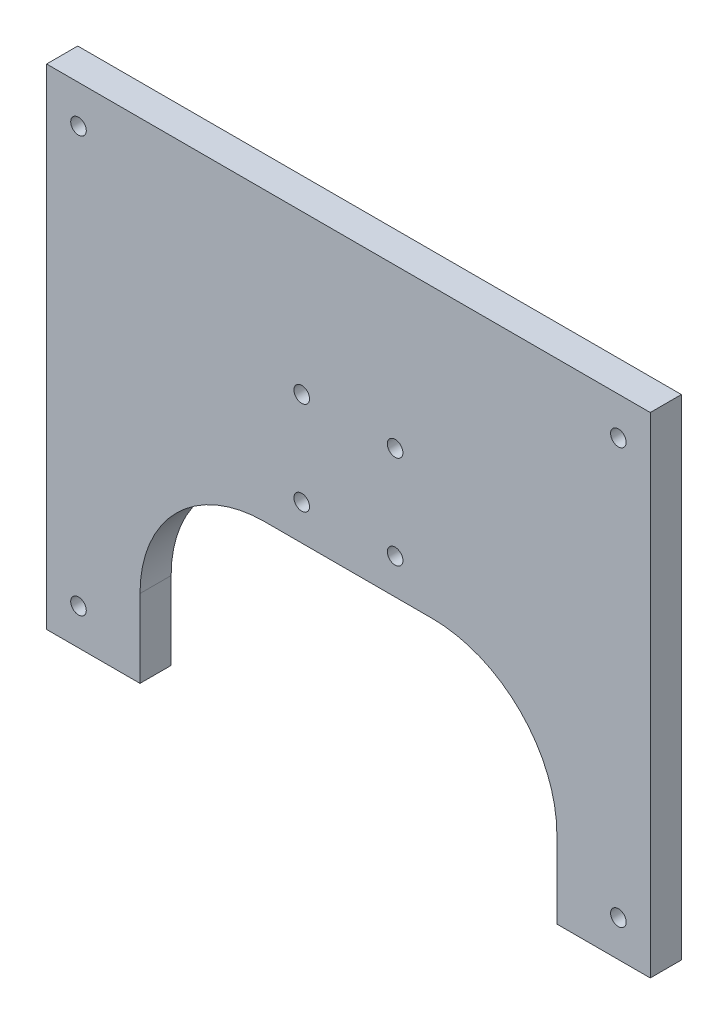
SolidWorks part; units mm, degrees
material "Beech"
ref_plane "Front Plane" through (0, 0, 0) normal (0, 0, 1) x (1, 0, 0)
ref_plane "Top Plane" through (0, 0, 0) normal (0, 1, 0) x (1, 0, 0)
ref_plane "Right Plane" through (0, 0, 0) normal (1, 0, 0) x (0, 0, -1)
sketch "Sketch1" plane through (0, 0, 0) normal (0, 0, 1) x (1, 0, 0)
  line L0 (258.9335, 10.7139) -> (12.7, 10.7139)
  line L1 (135.8167, -73.0143) -> (135.8167, 40.1583) construction
  line L2 (12.7, 10.7139) -> (12.7, -189.0518)
  line L3 (12.7, -189.0518) -> (50.8, -189.0518)
  line L4 (50.8, -189.0518) -> (50.8, -106.5018)
  line L5 (50.8, -106.5018) -> (220.8335, -106.5018)
  line L6 (135.8167, -205.9834) -> (135.8167, -73.0143) construction
  line L7 (135.8167, -106.5018) -> (135.8167, 10.7139) construction
  line L8 (271.3655, 10.7139) -> (0, 10.7139) construction
  line L9 (12.7, -189.0518) -> (12.7, 10.2705) construction
  line L10 (220.8335, -189.0518) -> (220.8335, -106.5018)
  line L11 (258.9335, -189.0518) -> (220.8335, -189.0518)
  line L12 (258.9335, 10.7139) -> (258.9335, -189.0518)
  dimension "D1" = 38.1
  dimension "D2" = 82.55
extrude "Boss-Extrude1" add sketch "Sketch1" against normal blind 12.7
hole_wizard "1/4 (0.25) Diameter Hole1" positions "Sketch4" profile "Sketch5" hole size "1/4" standard "ANSI Inch" end condition through all
sketch "Sketch4" plane through (0, 0, -12.7) normal (0, 0, -1) x (-1, 0, 0)
  point P0 (-25.7062, -174.2334)
  point P6 (-116.7667, -92.0643)
  point P9 (-154.8667, -92.0643)
  point P12 (-245.9273, -174.2334)
  point P15 (-154.8667, -53.9643)
  point P18 (-245.9273, -4.748)
  point P21 (-116.7667, -53.9643)
  point P24 (-25.7062, -4.748)
sketch "Sketch5" plane through (25.7062, -174.2334, -12.7) normal (1, 0, 0) x (0, 1, 0)
  line L0 (0, 0) -> (0, 12.7)
  line L1 (0, 12.7) -> (3.175, 12.7)
  line L2 (3.175, 12.7) -> (3.175, 0)
  line L5 (3.175, 0) -> (0, 0)
  line L11 (0, -6.35) -> (0, 107.95) construction
  dimension "Thru Hole Dia." = 6.35
  dimension "Thru Hole Depth" = 12.7
fillet "Fillet2" radius 50.8 2 edges at (220.8335, -106.5018, -6.35) (50.8, -106.5018, -6.35)
